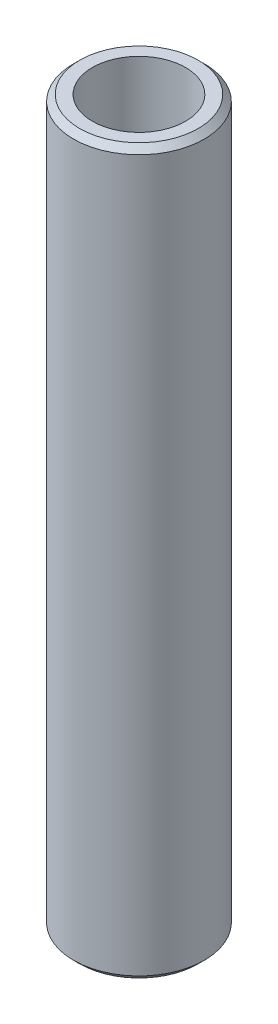
SolidWorks part; units mm, degrees
ref_plane "Front Plane" through (0, 0, 0) normal (0, 0, 1) x (1, 0, 0)
ref_plane "Top Plane" through (0, 0, 0) normal (0, 1, 0) x (1, 0, 0)
ref_plane "Right Plane" through (0, 0, 0) normal (1, 0, 0) x (0, 0, -1)
sketch "Sketch1" plane through (0, 0, 0) normal (0, 1, 0) x (1, 0, 0)
  circle A0 centre (0, 0) radius 22.5
  dimension "SHAFT_OD" = 45
extrude "Boss-Extrude1" add sketch "Sketch1" along normal blind 249.0697
sketch "Sketch2" plane through (0, 0, 0) normal (0, 1, 0) x (1, 0, 0)
  circle A0 centre (0, 0) radius 16.0479
  dimension "BORE_D" = 32.0958
extrude "Cut-Extrude1" cut sketch "Sketch2" along normal through all
chamfer "Chamfer1" distance 2.1021 angle 45 2 edges at (0, 249.0697, 22.5) (0, 0, 22.5)
